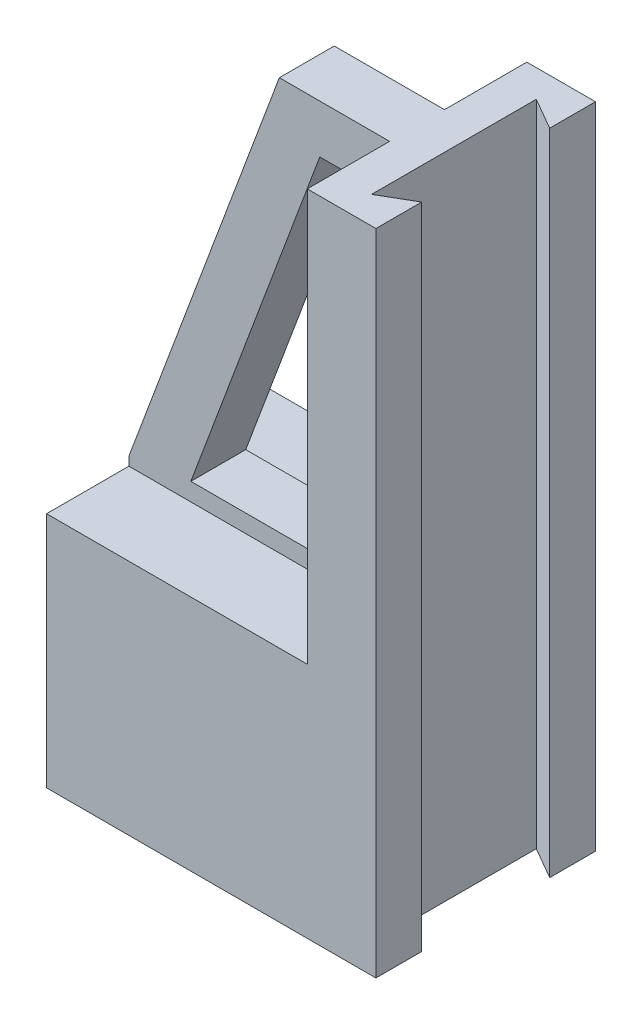
SolidWorks part; units mm, degrees
ref_plane "Спереди" through (0, 0, 0) normal (0, 0, 1) x (1, 0, 0)
ref_plane "Сверху" through (0, 0, 0) normal (0, 1, 0) x (1, 0, 0)
ref_plane "Справа" through (0, 0, 0) normal (1, 0, 0) x (0, 0, -1)
sketch "Эскиз1" plane through (0, 0, 0) normal (0, 0, 1) x (1, 0, 0)
  line L0 (0, 0) -> (120, 0)
  line L1 (120, 0) -> (120, 236.506)
  line L2 (120, 236.506) -> (54.8208, 236.506)
  line L3 (54.8208, 236.506) -> (0, 89.6655)
  line L4 (0, 89.6655) -> (0, 0)
  line L5 (22.5741, 93.0071) -> (69.5644, 218.873)
  line L6 (69.5644, 218.873) -> (93.564, 218.873)
  line L7 (93.564, 218.873) -> (93.564, 93.0071)
  line L8 (93.564, 93.0071) -> (22.5741, 93.0071)
extrude "Бобышка-Вытянуть1" add sketch "Эскиз1" along normal blind 80
sketch "Эскиз2" plane through (0, 236.506, 0) normal (0, 1, 0) x (1, 0, 0)
  line L0 (120, 0) -> (54.8208, 0) construction
  line L1 (0, -30) -> (95, -30)
  line L2 (0, -30) -> (0, 0)
  line L3 (0, 0) -> (95, 0)
  line L4 (95, -30) -> (95, 0)
  line L7 (0, -40) -> (125.8899, -40) construction
  line L10 (0, -80) -> (0, 0) construction
  line L11 (95, -50) -> (95, -80)
  line L12 (0, -80) -> (95, -80)
  line L13 (0, -50) -> (0, -80)
  line L14 (0, -50) -> (95, -50)
extrude "Вырез-Вытянуть1" cut sketch "Эскиз2" against normal blind 150
sketch "Эскиз3" plane through (0, 236.506, 0) normal (0, 1, 0) x (1, 0, 0)
  line L0 (108.4419, -10) -> (108.4419, -70)
  line L1 (108.4419, -70) -> (120, -63.327)
  line L2 (120, -63.327) -> (120, -16.673)
  line L3 (120, -16.673) -> (108.4419, -10)
  line L4 (120, -80) -> (120, 0) construction
extrude "Вырез-Вытянуть2" cut sketch "Эскиз3" against normal through all
